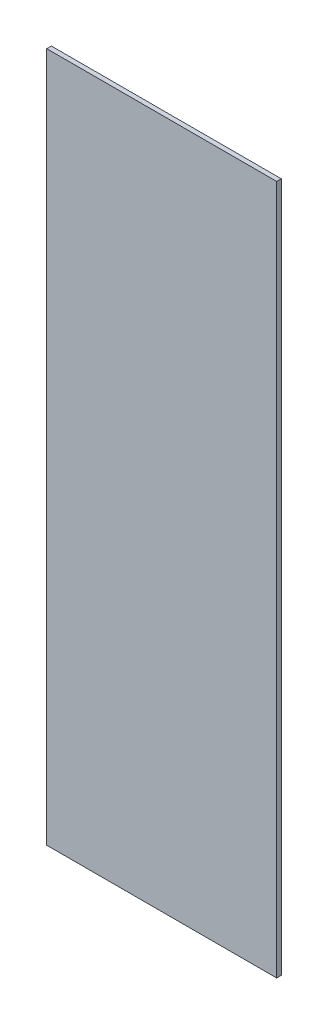
SolidWorks part; units mm, degrees
ref_plane "Front Plane" through (0, 0, 0) normal (0, 0, 1) x (1, 0, 0)
ref_plane "Top Plane" through (0, 0, 0) normal (0, 1, 0) x (1, 0, 0)
ref_plane "Right Plane" through (0, 0, 0) normal (1, 0, 0) x (0, 0, -1)
sketch "Sketch1" plane through (0, 0, 0) normal (0, 0, 1) x (1, 0, 0)
  line L1 (0, 0) -> (100, 0)
  line L2 (0, 0) -> (0, -300)
  line L3 (0, -300) -> (100, -300)
  line L4 (100, 0) -> (100, -300)
  dimension "D1" = 100
  dimension "D2" = 300
extrude "Boss-Extrude1" add sketch "Sketch1" along normal blind 2
sketch "Sketch3" plane through (0, 0, 2) normal (0, 0, 1) x (1, 0, 0)
  line L0 (10, 0) -> (10, -300) construction
  line L1 (100, 0) -> (0, 0) construction
  line L2 (0, -300) -> (100, -300) construction
  line L3 (0, 0) -> (0, -300) construction
  line L4 (100, -150) -> (0, -150) construction
  line L5 (100, -300) -> (100, 0) construction
  line L6 (100, -30) -> (0, -30)
  line L7 (100, -270) -> (0, -270)
  line L8 (100, -90) -> (0, -90) construction
  line L9 (100, -210) -> (0, -210) construction
  line L10 (50, 0) -> (50, -300) construction
  circle A0 centre (10, -30) radius 1.5
  circle A1 centre (10, -90) radius 1.5
  circle A2 centre (10, -150) radius 1.5
  circle A3 centre (10, -210) radius 1.5
  circle A4 centre (10, -270) radius 1.5
  circle A5 centre (90, -150) radius 1.5
  circle A6 centre (90, -90) radius 1.5
  circle A7 centre (90, -30) radius 1.5
  circle A8 centre (90, -270) radius 1.5
  circle A9 centre (90, -210) radius 1.5
  dimension "D4" = 3
  dimension "D1" = 10
  dimension "D2" = 30
  dimension "D3" = 60
